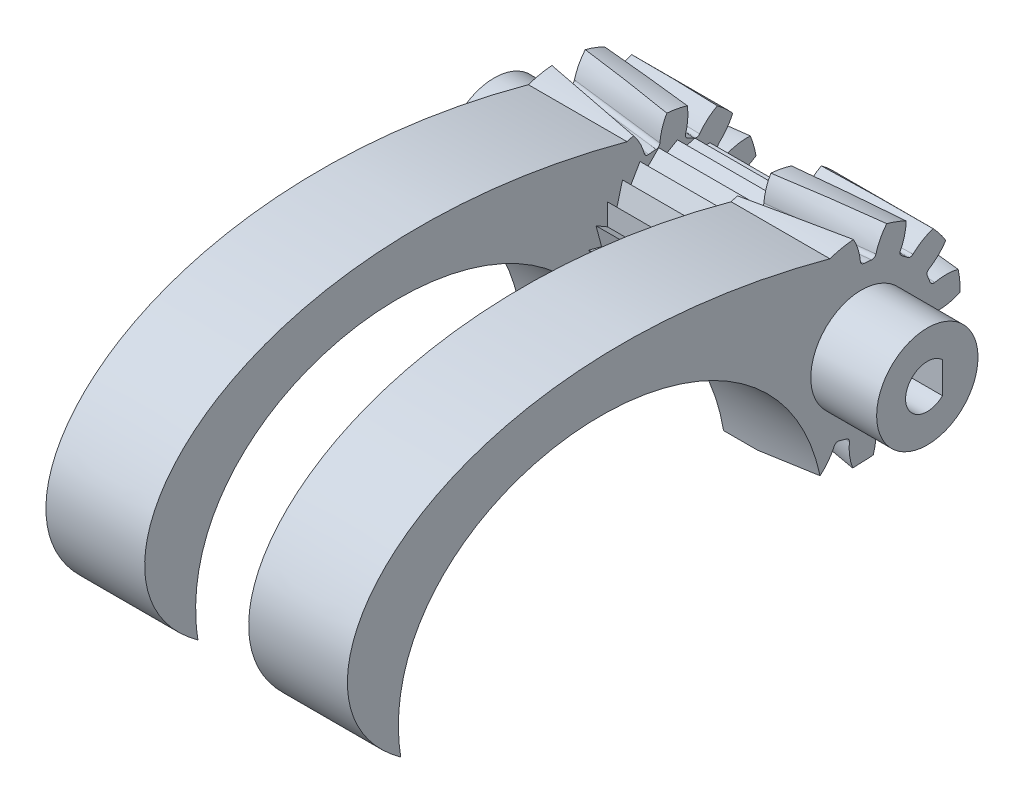
SolidWorks part; units mm, degrees
material "ABS"
ref_plane "Front Plane" through (0, 0, 0) normal (0, 0, 1) x (1, 0, 0)
ref_plane "Top Plane" through (0, 0, 0) normal (0, 1, 0) x (1, 0, 0)
ref_plane "Right Plane" through (0, 0, 0) normal (1, 0, 0) x (0, 0, -1)
sketch "Sketch1" plane through (0, 0, 0) normal (1, 0, 0) x (0, 0, -1)
  line L6 (0, 0) -> (-35, 0) construction
  line L7 (-35, 0) -> (-35, -9.3782) construction
  line L8 (-35, -9.3782) -> (0, 0) construction
  line L9 (-35, -9.3782) -> (0, -7.5)
  line L10 (-2.4038, 7.1043) -> (-33.2845, 15.4706) construction
  line L11 (-33.2845, 15.4706) -> (-46.3565, -1.1335) construction
  line L12 (-46.3565, -1.1335) -> (-35, -9.3782) construction
  circle A4 centre (0, 0) radius 1.5 construction
  arc A5 (0, -7.5) -> (-2.4038, 7.1043) centre (0, 0) ccw
  spline S0 degree 3 poles (-2.4038, 7.1043) (-33.2845, 15.4706) (-46.3565, -1.1335) (-35, -9.3782) knots 0 0 0 0 1 1 1 1
  point P7 (-19.8448, 5.1131)
  point P9 (-22.2147, 3.4645)
  point P11 (-15.5686, 7.0709)
  point P12 (-23.1936, 1.3006)
  point P13 (-15.4655, 5.1131)
  point P14 (-33.7039, 0.7339)
  point P15 (-38.7061, 4.3245)
  point P16 (-49.6825, 2.3095)
  point P17 (-15.3747, 9.9983)
  point P18 (-54.1897, 2.6807)
  point P19 (-23.5407, 4.7487)
  point P20 (0, 0)
  dimension "D2" = 3
  dimension "D4" = 15
  dimension "D3" = 7.5
  dimension "D1" = 35
  dimension "D5" = 31.9939
  dimension "D6" = 21.1322
  dimension "D7" = 14.0337
extrude "ClawShape" add sketch "Sketch1" along normal mid plane 7.5 contours L9 A5 | A5 S0 L9 region at (0, -0.1847, 16.1276)
sketch "GearProfile" plane through (0, 0, 0) normal (1, 0, 0) x (0, 0, -1)
  line L0 (0, 0) -> (0, 7.5) construction
  line L1 (-0.7835, 6.4526) -> (0.7835, 6.4526) construction
  line L2 (0, 0) -> (-0.5585, 5.4716) construction
  line L3 (0, 4.3) -> (-1.4813, 8.3699) construction
  line L4 (0, 0) -> (1.7949, 7.2821) construction
  line L5 (0.7835, 6.4526) -> (2.3049, 6.0776) construction
  arc A0 (0, -7.5) -> (-2.4038, 7.1043) centre (0, 0) ccw construction
  arc A1 (-0.5585, 5.4716) -> (-2.07, 8.2441) centre (-4.6172, 5.0573) ccw
  arc A2 (0.5585, 5.4716) -> (2.07, 8.2441) centre (4.6172, 5.0573) cw
  circle A3 centre (0, 0) radius 6.5 construction
  arc A4 (0.5585, 5.4716) -> (-0.5585, 5.4716) centre (0, 0) ccw
  circle A5 centre (0, 0) radius 2.94 construction
  arc A6 (2.07, 8.2441) -> (-2.07, 8.2441) centre (0, 0) ccw
  dimension "D3" = 5.88
  dimension "D1" = 13
  dimension "D4" = 1
  dimension "D5" = 20
  dimension "D6" = 13.846
sketch "Sketch4" plane through (0, 0, 0) normal (0, 1, 0) x (1, 0, 0)
  line L0 (-3.75, 7.5) -> (-3.75, -2.4038) construction
  line L1 (-3.75, 0.6612) -> (3.75, -0.6612)
  line L4 (-0.0247, 0) -> (0.0247, 0) construction
  line L5 (3.75, -2.4038) -> (3.75, 7.5) construction
  dimension "D1" = 10
  dimension "D2" = 7.6157
curve "HelixAngle"
sketch "Sketch5" plane through (3.75, 0, 0) normal (1, 0, 0) x (0, 0.0882, -0.9961)
  line L0 (0, 0) -> (0, 7.5) construction
  line L1 (-0.7835, 6.4526) -> (0.7835, 6.4526) construction
  line L2 (0, 0) -> (-0.5585, 5.4716) construction
  line L3 (0, 4.3) -> (-1.4813, 8.3699) construction
  line L4 (0, 0) -> (1.7949, 7.2821) construction
  line L5 (0.7835, 6.4526) -> (2.3049, 6.0776) construction
  arc A1 (-0.5585, 5.4716) -> (-2.07, 8.2441) centre (-4.6172, 5.0573) ccw
  arc A2 (0.5585, 5.4716) -> (2.07, 8.2441) centre (4.6172, 5.0573) cw
  circle A3 centre (0, 0) radius 6.5 construction
  arc A4 (0.5585, 5.4716) -> (-0.5585, 5.4716) centre (0, 0) ccw
  circle A5 centre (0, 0) radius 2.94 construction
  arc A6 (2.07, 8.2441) -> (-2.07, 8.2441) centre (0, 0) ccw
sketch "Sketch6" plane through (-3.75, 0, 0) normal (1, 0, 0) x (0, -0.0882, -0.9961)
  line L0 (0, 0) -> (0, 7.5) construction
  line L1 (-0.7835, 6.4526) -> (0.7835, 6.4526) construction
  line L2 (0, 0) -> (-0.5585, 5.4716) construction
  line L3 (0, 4.3) -> (-1.4813, 8.3699) construction
  line L4 (0, 0) -> (1.7949, 7.2821) construction
  line L5 (0.7835, 6.4526) -> (2.3049, 6.0776) construction
  arc A1 (-0.5585, 5.4716) -> (-2.07, 8.2441) centre (-4.6172, 5.0573) ccw
  arc A2 (0.5585, 5.4716) -> (2.07, 8.2441) centre (4.6172, 5.0573) cw
  circle A3 centre (0, 0) radius 6.5 construction
  arc A4 (0.5585, 5.4716) -> (-0.5585, 5.4716) centre (0, 0) ccw
  circle A5 centre (0, 0) radius 2.94 construction
  arc A6 (2.07, 8.2441) -> (-2.07, 8.2441) centre (0, 0) ccw
loft "GearCut" cut profiles "Sketch6", "Sketch5"
fillet "GearFillet" radius 0.3 2 edges
pattern_circular "GearPattern" count 7 every 31.667 about axis through (3.75, 0, 0) along (-1, 0, 0) of "GearCut", "GearFillet"
sketch "Sketch8" plane through (-3.75, 0, 0) normal (-1, 0, 0) x (0, 0, 1)
  circle A0 centre (0, 0) radius 3.85
  dimension "D2" = 7.7
extrude "Boss-Extrude1" add sketch "Sketch8" along normal blind 5
sketch "Sketch9" plane through (3.75, 0, 0) normal (1, 0, 0) x (0, 0, -1)
  line L0 (0, 0) -> (0, 5.5) construction
  line L1 (0, 0) -> (1.4235, 5.3126) construction
  line L2 (1.4235, 5.3126) -> (0, 4.4907)
  line L3 (0, 5.5) -> (0, 4.4907)
  line L4 (1.4235, 5.3126) -> (1.1623, 4.3377)
  line L5 (2.75, 4.7631) -> (1.1623, 4.3377)
  line L6 (2.75, 4.7631) -> (2.2454, 3.8891)
  line L7 (3.8891, 3.8891) -> (2.2454, 3.8891)
  line L8 (3.8891, 3.8891) -> (3.1754, 3.1754)
  line L9 (4.7631, 2.75) -> (3.1754, 3.1754)
  line L10 (4.7631, 2.75) -> (3.8891, 2.2454)
  line L11 (5.3126, 1.4235) -> (3.8891, 2.2454)
  line L12 (5.3126, 1.4235) -> (4.3377, 1.1623)
  line L13 (5.5, 0) -> (4.3377, 1.1623)
  line L14 (5.5, 0) -> (4.4907, 0)
  line L15 (5.3126, -1.4235) -> (4.4907, 0)
  line L16 (5.3126, -1.4235) -> (4.3377, -1.1623)
  line L17 (4.7631, -2.75) -> (4.3377, -1.1623)
  line L18 (4.7631, -2.75) -> (3.8891, -2.2454)
  line L19 (3.8891, -3.8891) -> (3.8891, -2.2454)
  line L20 (3.8891, -3.8891) -> (3.1754, -3.1754)
  line L21 (2.75, -4.7631) -> (3.1754, -3.1754)
  line L22 (2.75, -4.7631) -> (2.2454, -3.8891)
  line L23 (1.4235, -5.3126) -> (2.2454, -3.8891)
  line L24 (1.4235, -5.3126) -> (1.1623, -4.3377)
  line L25 (0, -5.5) -> (1.1623, -4.3377)
  line L26 (0, -5.5) -> (0, -4.4907)
  line L27 (-1.4235, -5.3126) -> (0, -4.4907)
  line L28 (-1.4235, -5.3126) -> (-1.1623, -4.3377)
  line L29 (-2.75, -4.7631) -> (-1.1623, -4.3377)
  line L30 (-2.75, -4.7631) -> (-2.2454, -3.8891)
  line L31 (-3.8891, -3.8891) -> (-2.2454, -3.8891)
  line L32 (-3.8891, -3.8891) -> (-3.1754, -3.1754)
  line L33 (-4.7631, -2.75) -> (-3.1754, -3.1754)
  line L34 (-4.7631, -2.75) -> (-3.8891, -2.2454)
  line L35 (-5.3126, -1.4235) -> (-3.8891, -2.2454)
  line L36 (-5.3126, -1.4235) -> (-4.3377, -1.1623)
  line L37 (-5.5, 0) -> (-4.3377, -1.1623)
  line L38 (-5.5, 0) -> (-4.4907, 0)
  line L39 (-5.3126, 1.4235) -> (-4.4907, 0)
  line L40 (-5.3126, 1.4235) -> (-4.3377, 1.1623)
  line L41 (-4.7631, 2.75) -> (-4.3377, 1.1623)
  line L42 (-4.7631, 2.75) -> (-3.8891, 2.2454)
  line L43 (-3.8891, 3.8891) -> (-3.8891, 2.2454)
  line L44 (-3.8891, 3.8891) -> (-3.1754, 3.1754)
  line L45 (-2.75, 4.7631) -> (-3.1754, 3.1754)
  line L46 (-2.75, 4.7631) -> (-2.2454, 3.8891)
  line L47 (-1.4235, 5.3126) -> (-2.2454, 3.8891)
  line L48 (-1.4235, 5.3126) -> (-1.1623, 4.3377)
  line L49 (0, 5.5) -> (-1.1623, 4.3377)
  arc A0 (1.4235, 5.3126) -> (0, 5.5) centre (0, 0) ccw construction
  circle A1 centre (0, 0) radius 5.5 construction
  point P77 (0, 0)
  dimension "D1" = 11
  dimension "D2" = 15
  dimension "D3" = 60
  dimension "D4" = 24
extrude "Boss-Extrude2" add sketch "Sketch9" along normal blind 3.95
ref_plane "Plane1" through (7.7, 0, 0) normal (1, 0, 0) x (0, 0, -1)
mirror "Mirror1" about plane through (7.7, 0, 0) normal (1, 0, 0) of bodies 107
sketch "Sketch10" plane through (19.15, 0, 0) normal (1, 0, 0) x (0, 0, -1)
  line L0 (-1.5, 0) -> (1, 0) construction
  line L1 (1, -1.118) -> (1, 1.118) construction
  line L2 (1.15, -1.1832) -> (1.15, 1.1832)
  arc A1 (1, 1.118) -> (1, -1.118) centre (0, 0) ccw construction
  arc A2 (1.15, 1.1832) -> (1.15, -1.1832) centre (0, 0) ccw
  point P8 (1, 0)
  dimension "D1" = 3
  dimension "D3" = 0.15
  dimension "D2" = 2.5
  dimension "D4" = 0.15
extrude "Cut-Extrude1" cut sketch "Sketch10" against normal through all both and the other way through all
sketch "Sketch11" plane through (19.15, 0, 0) normal (1, 0, 0) x (0, 0, -1)
  line L1 (-35, -9.3782) -> (-2.9802, -7.6599)
  line L2 (-35, -9.3782) -> (-36.6188, 0.6987) construction
  line L3 (-36.6188, 0.6987) -> (-28.4433, 9.9239) construction
  line L4 (-35, -9.3782) -> (-3.6132, -7.6939) construction
  line L6 (-5.7317, 9.0929) -> (-2.9802, -7.6599) construction
  line L7 (-28.4433, 9.9239) -> (-5.7317, 9.0929) construction
  spline S0 degree 4 poles (-35, -9.3782) (-36.6188, 0.6987) (-28.4433, 9.9239) (-5.7317, 9.0929) (-2.9802, -7.6599) knots 0 0 0 0 0 1 1 1 1 1
  point P1 (-56.4492, 14.9875)
  point P2 (-25.5451, -0.8509)
  point P6 (-47.6415, -0.5418)
  point P7 (-10.5566, 7.8023)
  point P9 (0, 0)
  point P10 (0, 0)
  dimension "D1" = 32.0659
  dimension "D2" = 10.2062
  dimension "D3" = 16.9772
  dimension "D4" = 22.7115
  dimension "D5" = 12.3265
extrude "Cut-Extrude2" cut sketch "Sketch11" against normal through all
equation "\"Moment Arm\"= 30mm"
equation "\"D1@ClawShape\" = \"Moment Arm\" / 4"
equation "\"Motor Shaft D\"= 5.88mm"
equation "\"Motor Screw\"= 3mm"
equation "\"Motor Shaft L\"= 5mm"
equation "\"D3@GearProfile\" = \"Motor Shaft D\""
equation "\"D2@GearProfile\" = \"Moment Arm\" / 30"
equation "\"Module\"= 1mm"
equation "\"Pitch D\"= \"Claw D\" - ( \"Moment Arm\" / 15 )"
equation "\"Number of Teeth\"= \"Pitch D\" / \"Module\""
equation "\"Claw D\"= \"Moment Arm\" / 2"
equation "\"D1@GearProfile\" = \"Pitch D\""
equation "\"D6@GearProfile\" = 180 / \"Number of Teeth\""
equation "\"HelixAngleAux\"= sqr ( ( ( \"Moment Arm\" / 8 ) ^ 2 ) + ( tan ( 10deg ) * ( \"Moment Arm\" / 8 ) ) ^ 2 )"
equation "\"D2@Sketch4\"=\"HelixAngleAux\"*2"
equation "\"D1@GearPattern\"=(\"Number of Teeth\"/360)*190"
equation "\"D1@Boss-Extrude2\"=\"Moment Arm\"/8+0.2mm"
